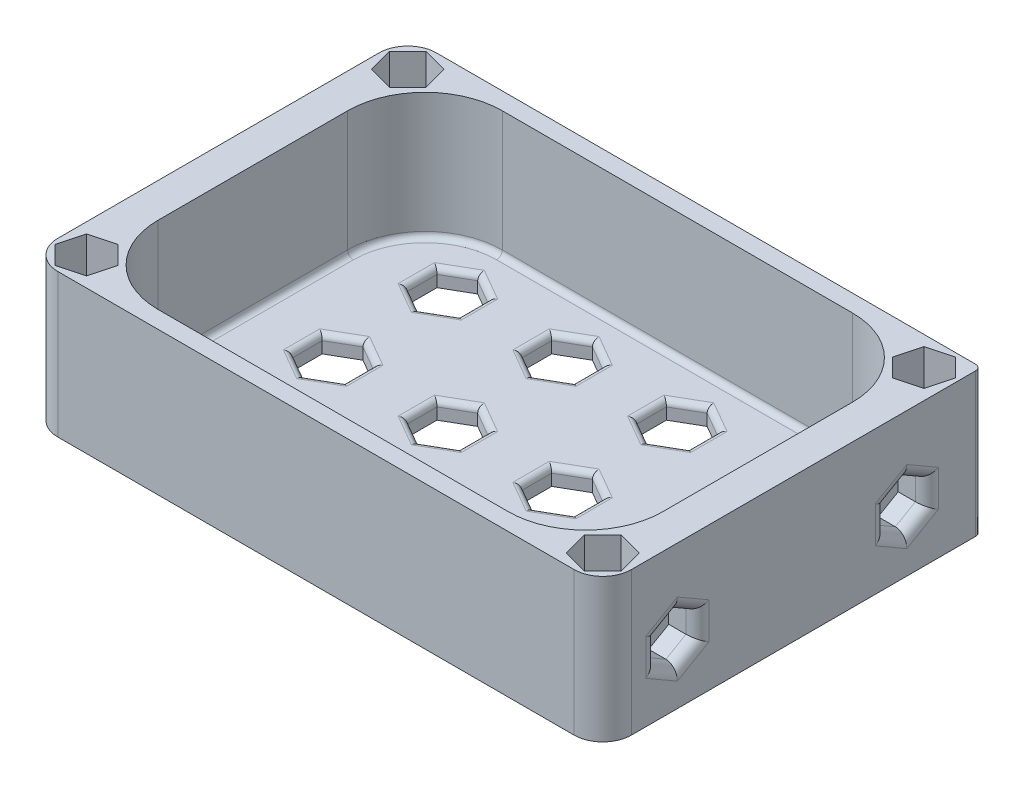
SolidWorks part; units mm, degrees
note: The reader was unsure of these and kept them because the rebuilt part matched: shared geometry of "Sketch3<7>".
ref_plane "Front Plane" through (0, 0, 0) normal (0, 0, 1) x (1, 0, 0)
ref_plane "Top Plane" through (0, 0, 0) normal (0, 1, 0) x (1, 0, 0)
ref_plane "Right Plane" through (0, 0, 0) normal (1, 0, 0) x (0, 0, -1)
sketch "Sketch3" plane through (0, 0, 0) normal (0, -1, 0) x (1, 0, 0)
  line L0 (-60, 20) -> (-80, 20)
  line L1 (-90, 23) -> (-100, 23)
  line L2 (-80, -5.1962) -> (-75.5, -2.5981)
  line L3 (-90, -23) -> (-100, -23)
  line L4 (-6, 23) -> (-6, -23)
  line L5 (-60, 0) -> (-40, 0)
  line L6 (-94, 23) -> (-94, -23)
  line L7 (-75.5, -2.5981) -> (-75.5, 2.5981)
  line L8 (-75.5, 2.5981) -> (-80, 5.1962)
  line L9 (-80, 5.1962) -> (-84.5, 2.5981)
  line L10 (-84.5, 2.5981) -> (-84.5, -2.5981)
  line L11 (-100, -23) -> (-100, -33)
  line L12 (-100, 23) -> (-100, 33)
  line L13 (-100, 33) -> (-10, 33)
  line L14 (-10, 33) -> (0, 33)
  line L15 (0, 33) -> (0, -23)
  line L16 (-90, 23) -> (-90, 33)
  line L17 (0, 33) -> (0, 23)
  line L18 (0, 23) -> (-10, 23)
  line L19 (-100, -33) -> (-10, -33)
  line L20 (-10, -33) -> (-10, -23)
  line L21 (-10, -33) -> (0, -33)
  line L22 (0, -33) -> (0, -23)
  line L23 (-10, 23) -> (-10, 33)
  line L24 (-90, -23) -> (-90, -33)
  line L49 (-10, -23) -> (0, -23)
  line L50 (-100, 33) -> (-90, 23)
  line L65 (0, 33) -> (-10, 23)
  line L67 (0, -33) -> (-10, -23)
  line L69 (-90, -23) -> (-100, -33)
  line L76 (-90, 30) -> (-10, 30)
  line L83 (-90, -30) -> (-10, -30)
  line L84 (-84.5, -2.5981) -> (-80, -5.1962)
  line L85 (-40, 0) -> (-20, 0)
  line L86 (-20, 0) -> (-20, 20)
  line L87 (-20, -20) -> (-20, 0)
  line L88 (-60, -20) -> (-40, -20)
  line L89 (-40, -20) -> (-20, -20)
  line L90 (-60, -20) -> (-60, 0)
  line L91 (-60, 20) -> (-40, 20)
  line L92 (-40, 20) -> (-20, 20)
  line L93 (-60, 0) -> (-60, 20)
  line L94 (-40, 20) -> (-40, 0)
  line L95 (-40, 0) -> (-40, -20)
  line L96 (0, 23) -> (0, -23)
  line L97 (0, 0) -> (-20, 0)
  line L98 (-80, -25.1962) -> (-75.5, -22.5981)
  line L99 (-55.5, 17.4019) -> (-55.5, 22.5981)
  line L100 (-55.5, 22.5981) -> (-60, 25.1962)
  line L101 (-60, 25.1962) -> (-64.5, 22.5981)
  line L102 (-64.5, 22.5981) -> (-64.5, 17.4019)
  line L103 (-64.5, 17.4019) -> (-60, 14.8038)
  line L104 (-60, 14.8038) -> (-55.5, 17.4019)
  line L105 (-35.5, 17.4019) -> (-35.5, 22.5981)
  line L106 (-35.5, 22.5981) -> (-40, 25.1962)
  line L107 (-40, 25.1962) -> (-44.5, 22.5981)
  line L108 (-44.5, 22.5981) -> (-44.5, 17.4019)
  line L109 (-44.5, 17.4019) -> (-40, 14.8038)
  line L110 (-40, 14.8038) -> (-35.5, 17.4019)
  line L111 (-24.5, 17.4019) -> (-20, 14.8038)
  line L112 (-20, 14.8038) -> (-15.5, 17.4019)
  line L113 (-15.5, 17.4019) -> (-15.5, 22.5981)
  line L114 (-15.5, 22.5981) -> (-20, 25.1962)
  line L115 (-20, 25.1962) -> (-24.5, 22.5981)
  line L116 (-24.5, 22.5981) -> (-24.5, 17.4019)
  line L117 (-24.5, 2.5981) -> (-24.5, -2.5981)
  line L118 (-24.5, -2.5981) -> (-20, -5.1962)
  line L119 (-20, -5.1962) -> (-15.5, -2.5981)
  line L120 (-15.5, -2.5981) -> (-15.5, 2.5981)
  line L121 (-15.5, 2.5981) -> (-20, 5.1962)
  line L122 (-20, 5.1962) -> (-24.5, 2.5981)
  line L123 (-40, 5.1962) -> (-44.5, 2.5981)
  line L124 (-44.5, 2.5981) -> (-44.5, -2.5981)
  line L125 (-44.5, -2.5981) -> (-40, -5.1962)
  line L126 (-40, -5.1962) -> (-35.5, -2.5981)
  line L127 (-35.5, -2.5981) -> (-35.5, 2.5981)
  line L128 (-35.5, 2.5981) -> (-40, 5.1962)
  line L129 (-60, 5.1962) -> (-64.5, 2.5981)
  line L130 (-64.5, 2.5981) -> (-64.5, -2.5981)
  line L131 (-64.5, -2.5981) -> (-60, -5.1962)
  line L132 (-60, -5.1962) -> (-55.5, -2.5981)
  line L133 (-55.5, -2.5981) -> (-55.5, 2.5981)
  line L134 (-55.5, 2.5981) -> (-60, 5.1962)
  line L135 (-64.5, -17.4019) -> (-64.5, -22.5981)
  line L136 (-64.5, -22.5981) -> (-60, -25.1962)
  line L137 (-60, -25.1962) -> (-55.5, -22.5981)
  line L138 (-55.5, -22.5981) -> (-55.5, -17.4019)
  line L139 (-55.5, -17.4019) -> (-60, -14.8038)
  line L140 (-60, -14.8038) -> (-64.5, -17.4019)
  line L141 (-44.5, -22.5981) -> (-40, -25.1962)
  line L142 (-40, -25.1962) -> (-35.5, -22.5981)
  line L143 (-35.5, -22.5981) -> (-35.5, -17.4019)
  line L144 (-35.5, -17.4019) -> (-40, -14.8038)
  line L145 (-40, -14.8038) -> (-44.5, -17.4019)
  line L146 (-44.5, -17.4019) -> (-44.5, -22.5981)
  line L147 (-20, -25.1962) -> (-15.5, -22.5981)
  line L148 (-15.5, -22.5981) -> (-15.5, -17.4019)
  line L149 (-15.5, -17.4019) -> (-20, -14.8038)
  line L150 (-20, -14.8038) -> (-24.5, -17.4019)
  line L151 (-24.5, -17.4019) -> (-24.5, -22.5981)
  line L152 (-24.5, -22.5981) -> (-20, -25.1962)
  line L153 (-8.1639, 31.1639) -> (-9.322, 26.8419)
  line L154 (-9.322, 26.8419) -> (-6.1581, 23.678)
  line L155 (-6.1581, 23.678) -> (-1.8361, 24.8361)
  line L156 (-1.8361, 24.8361) -> (-0.678, 29.1581)
  line L157 (-0.678, 29.1581) -> (-3.8419, 32.322)
  line L158 (-3.8419, 32.322) -> (-8.1639, 31.1639)
  line L165 (-99.322, -29.1581) -> (-96.1581, -32.322)
  line L166 (-96.1581, -32.322) -> (-91.8361, -31.1639)
  line L167 (-91.8361, -31.1639) -> (-90.678, -26.8419)
  line L168 (-90.678, -26.8419) -> (-93.8419, -23.678)
  line L169 (-93.8419, -23.678) -> (-98.1639, -24.8361)
  line L170 (-98.1639, -24.8361) -> (-99.322, -29.1581)
  line L171 (-1.8361, -24.8361) -> (-6.1581, -23.678)
  line L172 (-6.1581, -23.678) -> (-9.322, -26.8419)
  line L173 (-9.322, -26.8419) -> (-8.1639, -31.1639)
  line L174 (-8.1639, -31.1639) -> (-3.8419, -32.322)
  line L175 (-3.8419, -32.322) -> (-0.678, -29.1581)
  line L176 (-0.678, -29.1581) -> (-1.8361, -24.8361)
  line L183 (-99.322, 29.1581) -> (-98.1639, 24.8361)
  line L184 (-98.1639, 24.8361) -> (-93.8419, 23.678)
  line L185 (-93.8419, 23.678) -> (-90.678, 26.8419)
  line L186 (-90.678, 26.8419) -> (-91.8361, 31.1639)
  line L187 (-91.8361, 31.1639) -> (-96.1581, 32.322)
  line L188 (-96.1581, 32.322) -> (-99.322, 29.1581)
  line L189 (-75.5, -22.5981) -> (-75.5, -17.4019)
  line L190 (-100, -23) -> (-100, 23)
  line L191 (-75.5, -17.4019) -> (-80, -14.8038)
  line L192 (-80, -14.8038) -> (-84.5, -17.4019)
  line L193 (-84.5, -17.4019) -> (-84.5, -22.5981)
  line L194 (-84.5, -22.5981) -> (-80, -25.1962)
  line L195 (-80, 25.1962) -> (-84.5, 22.5981)
  line L196 (-84.5, 22.5981) -> (-84.5, 17.4019)
  line L197 (-84.5, 17.4019) -> (-80, 14.8038)
  line L198 (-80, 14.8038) -> (-75.5, 17.4019)
  line L199 (-75.5, 17.4019) -> (-75.5, 22.5981)
  line L200 (-75.5, 22.5981) -> (-80, 25.1962)
  line L201 (-80, 20) -> (-80, 0)
  line L202 (-80, 0) -> (-80, -20)
  line L203 (-80, -20) -> (-60, -20)
  line L204 (-60, 0) -> (-80, 0)
  arc A2 (-6, -16.5167) -> (-19.4833, -30) centre (-19.4833, -16.5167) cw
  circle A3 centre (-5, 28) radius 5
  circle A4 centre (-5, -28) radius 5
  circle A6 centre (-95, 28) radius 5
  circle A8 centre (-95, -28) radius 5
  arc A11 (-19.4833, 30) -> (-6, 16.5167) centre (-19.4833, 16.5167) cw
  circle A12 centre (-60, 20) radius 4.5
  circle A13 centre (-40, 20) radius 4.5
  arc A14 (-94, 16.5167) -> (-80.5167, 30) centre (-80.5167, 16.5167) cw
  arc A15 (-94, -16.5167) -> (-80.5167, -30) centre (-80.5167, -16.5167) ccw
  circle A16 centre (-95, 28) radius 3.875
  circle A17 centre (-5, 28) radius 3.875
  circle A18 centre (-5, -28) radius 3.875
  circle A19 centre (-95, -28) radius 3.875
  circle A20 centre (-20, 20) radius 4.5
  circle A21 centre (-20, -20) radius 4.5
  circle A22 centre (-40, -20) radius 4.5
  circle A23 centre (-60, -20) radius 4.5
  circle A24 centre (-60, 0) radius 4.5
  circle A25 centre (-40, 0) radius 4.5
  circle A26 centre (-20, 0) radius 4.5
  circle A27 centre (-60, 20) radius 4.5 construction
  circle A28 centre (-40, 20) radius 4.5 construction
  circle A29 centre (-20, 20) radius 4.5 construction
  circle A30 centre (-20, 0) radius 4.5 construction
  circle A31 centre (-40, 0) radius 4.5 construction
  circle A32 centre (-60, 0) radius 4.5 construction
  circle A33 centre (-60, -20) radius 4.5 construction
  circle A34 centre (-40, -20) radius 4.5 construction
  circle A35 centre (-20, -20) radius 4.5 construction
  circle A36 centre (-5, 28) radius 3.875 construction
  circle A37 centre (-95, 28) radius 3.875 construction
  circle A38 centre (-95, -28) radius 3.875 construction
  circle A39 centre (-5, -28) radius 3.875 construction
  circle A40 centre (-80, 0) radius 4.5 construction
  circle A41 centre (-80, -20) radius 4.5 construction
  circle A42 centre (-80, 20) radius 4.5 construction
  dimension "D5" = 3
  dimension "D3" = 10
  dimension "D8" = 9
  dimension "D4" = 7.75
  dimension "D9" = 20
  dimension "D12" = 100
  dimension "D1" = 6
  dimension "D2" = 3
  dimension "D6" = 60
  dimension "D7" = 6
  dimension "D10" = 20
  dimension "D11" = 20
extrude "Boss-Extrude7" add sketch "Sketch3" against normal blind 25 contours L21 A4 L67 | L67 A4 L22 | A4 L67 L175 L176 L171 L172 | A4 L67 L172 L173 L174 L175 | L22 A4 L49 | L49 A4 L67 A2 | A2 A4 L20 | L67 A4 A2 | L20 A4 L21 | A2 L20 L83 | L24 L83 L20 L19 | L97 L96 L49 L4 | A2 L4 L49 | L15 L97 L4 L18 | A11 L18 L4 | A11 L65 A3 L18 | A11 L23 A3 | A11 L76 L23 | A11 A3 L65 | A3 L65 L157 L158 L153 L154 | A3 L65 L154 L155 L156 L157 | L18 A3 L17 | L76 L16 L13 L23 | L14 A3 L23 | L24 A15 L83 | L19 A8 L24 | A8 L69 L165 L166 L167 L168 | A8 L69 L168 L169 L170 L165 | L3 A8 L11 | L69 A15 A8 | L3 A15 L69 A8 | A8 A15 L24 | L3 L190 L1 L6 | L6 A15 L3 | A14 L6 L1 | A14 L1 A6 L50 | A14 L50 A6 | A14 A6 L16 | A6 L50 L185 L186 L187 L188 | A6 L50 L188 L183 L184 L185 | L12 A6 L1 | L16 A6 L13 | A14 L16 L76
extrude "Boss-Extrude9" add sketch "Sketch3<7>" against normal blind 3
sketch "Sketch3<7>" plane through (0, 0, 0) normal (0, -1, 0) x (1, 0, 0) same geometry as "Sketch3"
sketch "Sketch5" plane through (-100, 0, 0) normal (-1, 0, 0) x (0, 0, 1)
  line L1 (-20, 6.4585) -> (-16.5, 8.4793)
  line L2 (-16.5, 8.4793) -> (-16.5, 12.5207)
  line L3 (-16.5, 12.5207) -> (-20, 14.5415)
  line L4 (-20, 14.5415) -> (-23.5, 12.5207)
  line L5 (-23.5, 12.5207) -> (-23.5, 8.4793)
  line L6 (-23.5, 8.4793) -> (-20, 6.4585)
  line L7 (23.5, 8.4793) -> (23.5, 12.5207)
  line L8 (23.5, 12.5207) -> (20, 14.5415)
  line L9 (20, 14.5415) -> (16.5, 12.5207)
  line L10 (16.5, 12.5207) -> (16.5, 8.4793)
  line L11 (16.5, 8.4793) -> (20, 6.4585)
  line L12 (20, 6.4585) -> (23.5, 8.4793)
  line L13 (-20, 10.5) -> (20, 10.5)
  line L18 (0, 0) -> (0, 10.5)
  line L19 (-28, 0) -> (28, 0) construction
  circle A0 centre (-20, 10.5) radius 3.5 construction
  circle A1 centre (20, 10.5) radius 3.5 construction
  circle A2 centre (-20, 10.5) radius 3.5
  circle A3 centre (20, 10.5) radius 3.5
  point P20 (0, 0)
  point P30 (0, 0)
  dimension "D3" = 7
  dimension "D1" = 40
  dimension "D2" = 10.5
extrude "Cut-Extrude1" cut sketch "Sketch5" against normal blind 5
sketch "Sketch6" plane through (0, 0, 0) normal (1, 0, 0) x (0, 0, -1)
  line L1 (-20, 6.4585) -> (-16.5, 8.4793)
  line L2 (-16.5, 8.4793) -> (-16.5, 12.5207)
  line L3 (-16.5, 12.5207) -> (-20, 14.5415)
  line L4 (-20, 14.5415) -> (-23.5, 12.5207)
  line L5 (-23.5, 12.5207) -> (-23.5, 8.4793)
  line L6 (-23.5, 8.4793) -> (-20, 6.4585)
  line L7 (20, 6.4585) -> (23.5, 8.4793)
  line L8 (23.5, 8.4793) -> (23.5, 12.5207)
  line L9 (23.5, 12.5207) -> (20, 14.5415)
  line L10 (20, 14.5415) -> (16.5, 12.5207)
  line L11 (16.5, 12.5207) -> (16.5, 8.4793)
  line L12 (16.5, 8.4793) -> (20, 6.4585)
  line L15 (0, 0) -> (0, 10.5)
  line L16 (-20, 10.5) -> (20, 10.5)
  circle A0 centre (-20, 10.5) radius 3.5 construction
  circle A1 centre (20, 10.5) radius 3.5 construction
  circle A2 centre (-20, 10.5) radius 3.5
  circle A3 centre (20, 10.5) radius 3.5
  dimension "D1" = 7
  dimension "D2" = 40
  dimension "D3" = 10.5
extrude "Cut-Extrude2" cut sketch "Sketch6" against normal blind 5 contours L4 L5 L6 L1 L2 L3 | L10 L11 L12 L7 L8 L9
fillet "Fillet3" radius 2 12 edges at (0, 10.5, -16.5) (0, 7.4689, -18.25) (0, 7.4689, -21.75) (0, 10.5, -23.5) (0, 13.5311, -21.75) (0, 13.5311, -18.25) (0, 7.4689, 21.75) (0, 10.5, 23.5) (0, 13.5311, 21.75) (0, 13.5311, 18.25) (0, 10.5, 16.5) (0, 7.4689, 18.25)
fillet "Fillet2" radius 1 1 edges at (0, 12.5, -33)
fillet "Fillet4" radius 1 44 edges at (-50, 3, -30) (-90.0508, 3, -26.0508) (-94, 3, 0) (-44.5, 3, 0) (-35.5, 3, 0) (-55.5, 3, 20) (-64.5, 3, 20) (-75.5, 3, 0) (-82.25, 3, 3.8971) (-84.5, 3, 0) (-82.25, 3, -3.8971) (-55.5, 3, 0) (-64.5, 3, 0) (-35.5, 3, 20) (-44.5, 3, 20) (-44.5, 3, -20) (-35.5, 3, -20) (-24.5, 3, 0) (-17.75, 3, -3.8971) (-15.5, 3, 0) (-17.75, 3, 3.8971) (-90.0508, 3, 26.0508) (-50, 3, 30) (-9.9492, 3, 26.0508) (-6, 3, 0) (-9.9492, 3, -26.0508) (-17.75, 3, 16.1029) (-15.5, 3, 20) (-17.75, 3, 23.8971) (-24.5, 3, 20) (-75.5, 3, 20) (-82.25, 3, 23.8971) (-84.5, 3, 20) (-82.25, 3, 16.1029) (-82.25, 3, -16.1029) (-84.5, 3, -20) (-82.25, 3, -23.8971) (-75.5, 3, -20) (-24.5, 3, -20) (-17.75, 3, -23.8971) (-15.5, 3, -20) (-17.75, 3, -16.1029) (-64.5, 3, -20) (-55.5, 3, -20)
